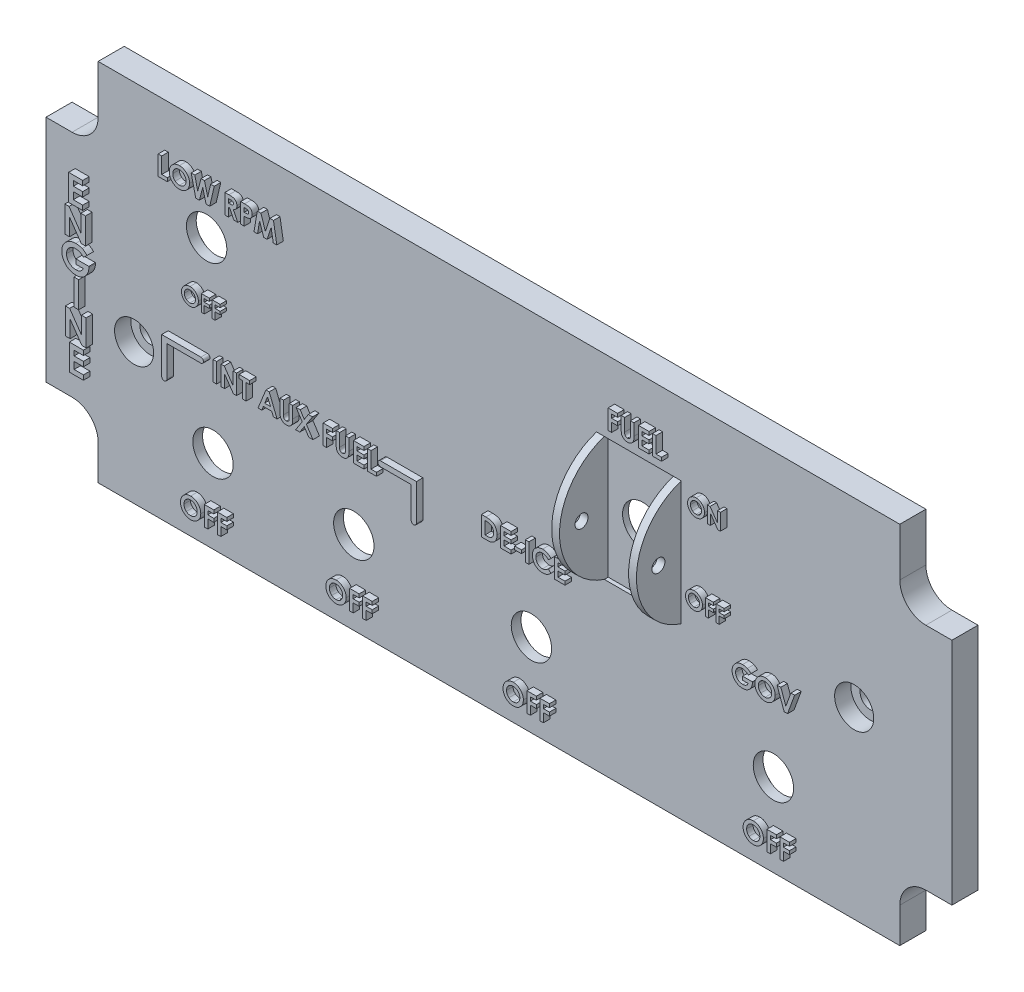
SolidWorks part; units mm, degrees
ref_plane "Front Plane" through (0, 0, 0) normal (0, 0, 1) x (1, 0, 0)
ref_plane "Top Plane" through (0, 0, 0) normal (0, 1, 0) x (1, 0, 0)
ref_plane "Right Plane" through (0, 0, 0) normal (1, 0, 0) x (0, 0, -1)
sketch "Sketch1" plane through (0, 0, 0) normal (0, 0, 1) x (1, 0, 0)
  line L5 (69.5, 52) -> (69.5, 0) construction
  line L6 (0, 0) -> (0, 67.4669) construction
  line L11 (131, 52) -> (131, 0) construction
  line L22 (0, 0) -> (131, 0) construction
  line L23 (8, 0) -> (8, 67.4669) construction
  line L25 (139, 0) -> (139, 68.7864) construction
  line L33 (0, 56) -> (139, 56)
  line L70 (8, 56) -> (8, 48.587)
  line L71 (4, 44.587) -> (0, 44.587)
  line L72 (0, 44.587) -> (0, 9.3797)
  line L73 (0, 9.3797) -> (4, 9.3797)
  line L74 (8, 5.3797) -> (8, 0)
  line L75 (8, 0) -> (131, 0)
  line L76 (131, 5.3797) -> (131, 0)
  line L77 (139, 9.3797) -> (135, 9.3797)
  line L78 (139, 44.587) -> (139, 9.3797)
  line L79 (135, 44.587) -> (139, 44.587)
  line L80 (131, 56) -> (131, 48.587)
  line L82 (139, 56) -> (139, 46.463)
  arc A14 (4, 9.3797) -> (8, 5.3797) centre (4, 5.3797) cw
  arc A16 (8, 48.587) -> (4, 44.587) centre (4, 48.587) cw
  arc A66 (131, 48.587) -> (135, 44.587) centre (135, 48.587) ccw
  arc A67 (135, 9.3797) -> (131, 5.3797) centre (135, 5.3797) ccw
  circle A99 centre (13.5185, 21.5) radius 1.6 construction
  circle A100 centre (124, 28.1942) radius 1.6 construction
  circle A101 centre (111.6129, 12.7439) radius 3.1 construction
  circle A102 centre (90.9664, 35.5) radius 3.1 construction
  circle A103 centre (74.4802, 12.7439) radius 3.1 construction
  circle A104 centre (47.23, 12.7439) radius 3.1 construction
  circle A105 centre (25.6233, 12.7439) radius 3.1 construction
  circle A106 centre (24.6456, 40.9066) radius 3.1 construction
  circle A107 centre (13.5185, 21.5) radius 1.6
  circle A108 centre (124, 28.1942) radius 1.6
  circle A109 centre (111.6129, 12.7439) radius 3.1
  circle A110 centre (90.9664, 35.5) radius 3.1
  circle A111 centre (74.4802, 12.7439) radius 3.1
  circle A112 centre (47.23, 12.7439) radius 3.1
  circle A113 centre (25.6233, 12.7439) radius 3.1
  circle A114 centre (24.6456, 40.9066) radius 3.1
  point P31 (8, 9.3797)
  point P34 (8, 44.587)
  point P37 (8, 42.463)
  point P54 (131, 42.463)
  point P55 (131, 44.587)
  point P56 (131, 9.3797)
  dimension "D3" = 123
  dimension "D4" = 56
  dimension "D5" = 4
  dimension "D1" = 8
  dimension "D2" = 139
extrude "Extrusion base" add sketch "Sketch1" along normal blind 4 contours A67 L77 L78 L79 A66 L80 L82 L33 L70 A16 L71 L72 L73 A14 L74 L75 L76 A114 A113 A112 A111 A110 A109 A108 A107 region at (69.6779, 28.095, 0)
sketch "Sketch4" plane through (0, 0, 4) normal (0, 0, 1) x (1, 0, 0)
  line L0 (7.8131, 40.4488) -> (7.8131, 12.7205) construction
  line L1 (13.9628, 3.2721) -> (122.5371, 3.2721) construction
  line L2 (21.6269, 23.2114) -> (124.0329, 23.2114) construction
  line L3 (-3.8412, 35.9988) -> (13.9628, 35.9988) construction
  line L4 (-4.2039, 31.4988) -> (13.9628, 31.4988) construction
  line L5 (52.3294, 25.1854) -> (57.4309, 25.1854) construction
  line L6 (3.2481, 12.7205) -> (3.2481, 40.9499) construction
  line L7 (57.4309, 25.1854) -> (57.4309, 20.0329) construction
  line L9 (24.7566, 25.1854) -> (19.1498, 25.1854) construction
  line L10 (19.1498, 25.1854) -> (19.1498, 20.0329) construction
  line L11 (52.3294, 25.5854) -> (57.8309, 25.5854)
  line L12 (57.8309, 25.5854) -> (57.8309, 20.0329)
  line L13 (24.7566, 24.7854) -> (19.5498, 24.7854)
  line L14 (19.5498, 24.7854) -> (19.5498, 20.0329)
  line L15 (52.3294, 24.7854) -> (57.0309, 24.7854)
  line L16 (57.0309, 24.7854) -> (57.0309, 20.0329)
  line L17 (24.7566, 25.5854) -> (18.7498, 25.5854)
  line L18 (18.7498, 25.5854) -> (18.7498, 20.0329)
  line L19 (-3.263, 26.9988) -> (14.747, 26.9988) construction
  line L20 (14.747, 22.4988) -> (-3.8454, 22.4988) construction
  line L21 (14.747, 17.9988) -> (-4.2039, 17.9988) construction
  line L22 (15.0682, 13.4988) -> (-4.2039, 13.4988) construction
  arc A0 (52.3294, 25.5854) -> (52.3294, 24.7854) centre (52.3294, 25.1854) ccw
  arc A1 (57.8309, 20.0329) -> (57.0309, 20.0329) centre (57.4309, 20.0329) cw
  arc A2 (24.7566, 24.7854) -> (24.7566, 25.5854) centre (24.7566, 25.1854) ccw
  arc A3 (19.5498, 20.0329) -> (18.7498, 20.0329) centre (19.1498, 20.0329) cw
  text T0 "<b>E</b>" font "Century Gothic" height 4
  text T1 "<b>OFF</b>" font "Century Gothic" height 2.5
  text T2 "<b>INT AUX FUEL</b>" font "Century Gothic" height 3
  text T3 "<b>OFF</b>" font "Century Gothic" height 2.5
  text T4 "<b>LOW RPM</b>" font "Century Gothic" height 3
  text T5 "<b>FUEL</b>" font "Century Gothic" height 3
  text T6 "<b>DE-ICE</b>" font "Century Gothic" height 3
  text T7 "<b>N</b>" font "Century Gothic" height 4
  text T8 "<b>GOV</b>" font "Century Gothic" height 3
  text T9 "<b>ON</b>" font "Century Gothic" height 2.5
  text T10 "<b>OFF</b>" font "Century Gothic" height 3
  text T11 "<b>OFF</b>" font "Century Gothic" height 3
  text T12 "<b>OFF</b>" font "Century Gothic" height 3
  text T13 "<b>OFF</b>" font "Century Gothic" height 3
  text T14 "<b>G</b>" font "Century Gothic" height 4
  text T15 "<b>I</b>" font "Century Gothic" height 4
  text T16 "<b>N</b>" font "Century Gothic" height 4
  text T17 "<b>E</b>" font "Century Gothic" height 4
  dimension "D1" = 4.5
  dimension "D2" = 0.4
  dimension "D4" = 0.4
  dimension "D5" = 4.5
  dimension "D6" = 4.5
  dimension "D7" = 4.5
  dimension "D8" = 4.5
extrude "Textos" add sketch "Sketch4" along normal blind 1
sketch "Sketch5" plane through (0, 0, 4) normal (0, 0, 1) x (1, 0, 0)
  line L1 (97.4664, 45) -> (84.4664, 45)
  line L2 (97.4664, 45) -> (97.4664, 26)
  line L3 (97.4664, 26) -> (84.4664, 26)
  line L4 (84.4664, 45) -> (84.4664, 26)
  circle A0 centre (90.9664, 35.5) radius 3.1 construction
  dimension "D1" = 13
  dimension "D2" = 6.5
  dimension "D3" = 19
  dimension "D4" = 9.5
extrude "Deprimido Fuel" cut sketch "Sketch5" against normal blind 0.6
sketch "Sketch6" plane through (0, 0, 3.4) normal (0, 0, 1) x (1, 0, 0)
  line L0 (97.4664, 45) -> (84.4664, 45) construction
  line L1 (97.4664, 26) -> (96.2664, 26)
  line L2 (97.4664, 26) -> (97.4664, 45)
  line L3 (97.4664, 45) -> (96.2664, 45)
  line L4 (96.2664, 26) -> (96.2664, 45)
  line L5 (84.4664, 26) -> (97.4664, 26) construction
  line L6 (85.6664, 26) -> (84.4664, 26)
  line L7 (85.6664, 26) -> (85.6664, 45)
  line L8 (85.6664, 45) -> (84.4664, 45)
  line L9 (84.4664, 26) -> (84.4664, 45)
  dimension "D1" = 1.2
extrude "Protectores Fuel" add sketch "Sketch6" along normal blind 7.6
sketch "Sketch7" plane through (97.4664, 0, 0) normal (1, 0, 0) x (0, 0, -1)
  line L1 (-4, 45) -> (-11, 45)
  line L2 (-11, 45) -> (-11, 26)
  line L3 (-11, 26) -> (-4, 26)
  line L4 (-4, 26) -> (-4, 45) construction
  arc A0 (-4, 26) -> (-4, 45) centre (-0.8775, 35.5) cw
  circle A1 centre (-7.5, 35.5) radius 1
  dimension "D1" = 10
  dimension "D2" = 2
  dimension "D3" = 3.5
extrude "Forma circular protectores" cut sketch "Sketch7" against normal up to surface (13 mm away) up to face at (84.4664, 35.5, 7.5)
sketch "Sketch8" plane through (0, 0, 0) normal (0, 0, -1) x (-1, 0, 0)
  circle A0 centre (-90.9664, 35.5) radius 6.6
  circle A1 centre (-111.6129, 12.7439) radius 6.6
  circle A2 centre (-74.4802, 12.7439) radius 6.6
  circle A3 centre (-47.23, 12.7439) radius 6.6
  circle A4 centre (-25.6233, 12.7439) radius 6.6
  circle A5 centre (-24.6456, 40.9066) radius 6.6
  dimension "D1" = 13.2
extrude "Back holes" cut sketch "Sketch8" against normal blind 2.5
sketch "Sketch9" plane through (0, 0, 4) normal (0, 0, 1) x (1, 0, 0)
  circle A0 centre (124, 28.1942) radius 3
  circle A1 centre (13.5185, 21.5) radius 3
  dimension "D1" = 6
extrude "Cut-Extrude4" cut sketch "Sketch9" against normal blind 2.5
